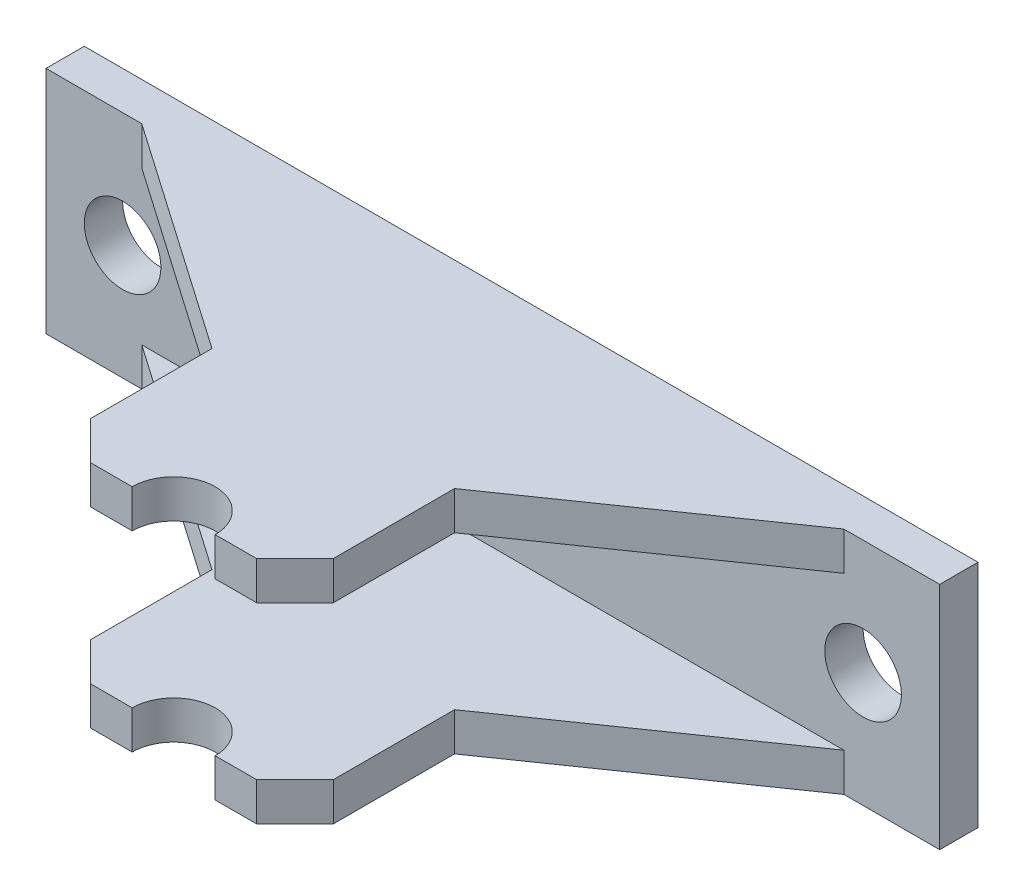
SolidWorks part; units mm, degrees
ref_plane "Front Plane" through (0, 0, 0) normal (0, 0, 1) x (1, 0, 0)
ref_plane "Top Plane" through (0, 0, 0) normal (0, 1, 0) x (1, 0, 0)
ref_plane "Right Plane" through (0, 0, 0) normal (1, 0, 0) x (0, 0, -1)
sketch "Sketch1" plane through (0, 0, 0) normal (0, 1, 0) x (1, 0, 0)
  line L1 (0, 0) -> (55, 0) construction
  line L2 (0, 0) -> (0, 25) construction
  line L3 (0, 25) -> (55, 25) construction
  line L4 (55, 0) -> (55, 25) construction
  line L6 (0, 25) -> (55, 25)
  line L10 (18, 0) -> (24.25, 0)
  line L11 (27.5, 0) -> (27.5, 25) construction
  line L13 (37, 0) -> (30.75, 0)
  line L14 (18, 0) -> (18, 12.5)
  line L15 (18, 12.5) -> (0, 25)
  line L16 (37, 12.5) -> (55, 25)
  line L17 (37, 0) -> (37, 12.5)
  circle A0 centre (27.5, 0) radius 3.25 construction
  arc A1 (24.25, 0) -> (30.75, 0) centre (27.5, 0) cw
  point P12 (0, 0)
  point P14 (27.5, 12.5)
  dimension "D1" = 6.5
  dimension "D2" = 55
  dimension "D3" = 25
  dimension "D4" = 18
extrude "Boss-Extrude1" add sketch "Sketch1" along normal blind 3
sketch "Sketch2" plane through (0, 0, -25) normal (0, 0, -1) x (-1, 0, 0)
  line L0 (-55, 3) -> (0, 3) construction
  line L1 (-62.5, 3) -> (7.5, 3)
  line L2 (-62.5, 3) -> (-62.5, -15)
  line L3 (-62.5, -15) -> (7.5, -15)
  line L4 (7.5, 3) -> (7.5, -15)
  line L5 (-27.5, 3) -> (-27.5, -15) construction
  line L6 (-62.5, -6) -> (-56.5, -6) construction
  circle A0 centre (-56.5, -6) radius 3
  circle A1 centre (1.5, -6) radius 3
  point P6 (-27.5, 3)
  point P7 (-27.5, 3)
  dimension "D3" = 6
  dimension "D1" = 70
  dimension "D2" = 18
  dimension "D4" = 6
extrude "Boss-Extrude2" add sketch "Sketch2" along normal blind 3
ref_plane "Plane1" through (0, -6, 0) normal (0, 1, 0) x (1, 0, 0)
mirror "Mirror1" about plane through (0, -6, 0) normal (0, 1, 0) of "Boss-Extrude1"
chamfer "Chamfer1" distance 3 angle 45 4 edges at (37, 1.5, 0) (18, 1.5, 0) (37, -13.5, 0) (18, -13.5, 0)
